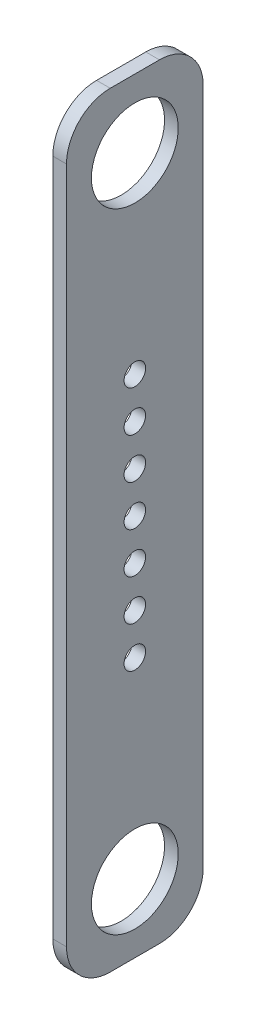
SolidWorks part; units mm, degrees
ref_plane "Front Plane" through (0, 0, 0) normal (1, 0, 0) x (0, 1, 0)
ref_plane "Top Plane" through (0, 0, 0) normal (0, 0, 1) x (0, 1, 0)
ref_plane "Right Plane" through (0, 0, 0) normal (0, 1, 0) x (-1, 0, 0)
sketch "Sketch1" plane through (0, 0, 0) normal (1, 0, 0) x (0, 1, 0)
  line L0 (38.1, 0) -> (-38.1, 0) construction
  line L1 (44.45, -7.9375) -> (-44.45, -7.9375)
  line L2 (44.45, -7.9375) -> (44.45, 7.9375)
  line L3 (44.45, 7.9375) -> (-44.45, 7.9375)
  line L4 (-44.45, -7.9375) -> (-44.45, 7.9375)
  line L5 (44.45, -7.9375) -> (-44.45, 7.9375) construction
  line L6 (44.45, 7.9375) -> (-44.45, -7.9375) construction
  point P0 (0, 0)
  point P9 (0, 0)
  dimension "D1" = 88.9
  dimension "D2" = 15.875
  dimension "D3" = 6.35
base flange "Base-Flange1" sketch "Sketch1" thickness 1.5875 reverse thickness direction no parameters "D1"=0.7366
sketch "Sketch6" plane through (0, 0, 0) normal (1, 0, 0) x (0, 1, 0)
  line L0 (44.45, 7.9375) -> (-44.45, 7.9375) construction
  line L1 (23.114, -7.9375) -> (-23.114, -7.9375) construction
  line L2 (23.114, -7.9375) -> (23.114, 7.9375)
  line L3 (23.114, 7.9375) -> (-23.114, 7.9375) construction
  line L4 (-23.114, -7.9375) -> (-23.114, 7.9375)
  line L5 (23.114, -7.9375) -> (-23.114, 7.9375) construction
  line L6 (23.114, 7.9375) -> (-23.114, -7.9375) construction
  point P0 (0, 0)
  dimension "D1" = 46.228
sketch "Sketch9" plane through (-1.5875, 0, 0) normal (-1, 0, 0) x (0, -1, 0)
  point P6 (0, 0)
  point P14 (-20.5228, 0)
  point P15 (-17.5777, 0)
hole_wizard "Ø2.5mm Dowel Hole1" positions "Sketch9" profile "Sketch10" hole size "Ø2.5" standard "ANSI Metric" end condition through all
sketch "Sketch10" plane through (-1.5875, 0, 0) normal (0, 1, 0) x (0, 0, 1)
  line L0 (0, 0) -> (0, 1.5875)
  line L1 (0, 1.5875) -> (1.25, 1.5875)
  line L2 (1.25, 1.5875) -> (1.25, 0)
  line L5 (1.25, 0) -> (0, 0)
  line L11 (0, -6.35) -> (0, 107.95) construction
  dimension "Thru Hole Dia." = 2.5
  dimension "Thru Hole Depth" = 1.5875
pattern_linear "LPattern1" count 4 spacing 4.75 along (0, -1, 0) count 4 spacing 4.75 along (0, 1, 0) of "Ø2.5mm Dowel Hole1"
fillet "Fillet1" radius 5.08 4 edges at (-0.7937, 44.45, 7.9375) (-0.7937, 44.45, -7.9375) (-0.7937, -44.45, 7.9375) (-0.7937, -44.45, -7.9375)
sketch "Sketch12" plane through (-1.5875, 0, 0) normal (-1, 0, 0) x (0, -1, 0)
  line L0 (-39.37, 7.9375) -> (39.37, 7.9375) construction
  line L2 (-44.45, -2.8575) -> (-44.45, 2.8575) construction
  line L3 (44.45, 2.8575) -> (44.45, -2.8575) construction
  point P0 (-36.5125, 0)
  point P8 (36.5125, 0)
  dimension "D1" = 7.9375
  dimension "D2" = 7.9375
  dimension "D3" = 7.9375
  dimension "D4" = 7.9375
hole_wizard "3/8 Clearance Hole1" positions "Sketch12" profile "Sketch13" hole size "3/8" standard "ANSI Inch" end condition through all
sketch "Sketch13" plane through (-1.5875, 36.5125, 0) normal (0, 1, 0) x (0, 0, 1)
  line L0 (0, 0) -> (0, 1.5875)
  line L1 (0, 1.5875) -> (5.0419, 1.5875)
  line L2 (5.0419, 1.5875) -> (5.0419, 0)
  line L5 (5.0419, 0) -> (0, 0)
  line L11 (0, -6.35) -> (0, 107.95) construction
  dimension "Thru Hole Dia." = 10.0838
  dimension "Thru Hole Depth" = 1.5875
sketch "Bend-Lines1" [suppressed] plane through (0, 0, 0) normal (0, 1, 0) x (1, 0, 0)
sketch "Bounding-Box1" [suppressed] plane through (0, 0, 0) normal (0, 1, 0) x (1, 0, 0)
sheet metal parameters "Sheet-Metal1" thickness 1.5875 parameters "D1"=0.7366
flat pattern "Flat-Pattern1" [suppressed]
sketch "Bend-Lines2" plane through (0, 0, 0) normal (1, 0, 0) x (0, 0, -1)
  line L0 (-6.35, -21.9918) -> (6.35, -21.9918) construction
  line L1 (6.35, 21.9918) -> (-6.35, 21.9918) construction
  line L2 (-6.35, -21.9918) -> (6.35, -21.9918) construction
  line L3 (6.35, 21.9918) -> (-6.35, 21.9918) construction
sketch3d "Bounding-Box2" [suppressed]
  line L0 (6.35, 41.275, 0) -> (6.35, -41.275, 0) construction
  line L1 (-6.35, 41.275, 0) -> (-6.35, -41.275, 0) construction
  line L2 (6.35, 41.275, 0) -> (-6.35, 41.275, 0) construction
  line L3 (6.35, -41.275, 0) -> (-6.35, -41.275, 0) construction
sheet metal parameters "Sheet-Metal3" thickness 1.5875 parameters "D1"=0.7366
flat pattern "Flat-Pattern1"
sketch "Bend-Lines2" plane through (0, 0, 0) normal (1, 0, 0) x (0, 0, -1)
  line L0 (-7.9375, -21.9918) -> (7.9375, -21.9918) construction
  line L1 (7.9375, 21.9918) -> (-7.9375, 21.9918) construction
  line L2 (-7.9375, -21.9918) -> (7.9375, -21.9918) construction
  line L3 (7.9375, 21.9918) -> (-7.9375, 21.9918) construction
sketch3d "Bounding-Box2" [suppressed]
  line L0 (7.9375, 44.45, 0) -> (7.9375, -44.45, 0) construction
  line L1 (-7.9375, 44.45, 0) -> (-7.9375, -44.45, 0) construction
  line L2 (7.9375, 44.45, 0) -> (-7.9375, 44.45, 0) construction
  line L3 (7.9375, -44.45, 0) -> (-7.9375, -44.45, 0) construction
bend of the flat pattern "Flatten-<SketchBend1>1"
bend of the flat pattern "Flatten-<SketchBend2>1"
sheet metal parameters "Sheet-Metal4" thickness 1.5875 parameters "D1"=0.7366
flat pattern "Flat-Pattern1"
sketch "Bend-Lines2" plane through (0, 0, 0) normal (1, 0, 0) x (0, 0, -1)
sketch3d "Bounding-Box2" [suppressed]
  line L0 (7.9375, -44.45, 0) -> (7.9375, 44.45, 0) construction
  line L1 (-7.9375, -44.45, 0) -> (-7.9375, 44.45, 0) construction
  line L2 (7.9375, -44.45, 0) -> (-7.9375, -44.45, 0) construction
  line L3 (7.9375, 44.45, 0) -> (-7.9375, 44.45, 0) construction
sheet metal parameters "Sheet-Metal5" thickness 1.5875 parameters "D1"=0.7366
flat pattern "Flat-Pattern1"
sketch "Bend-Lines2" plane through (0, 0, 0) normal (1, 0, 0) x (0, 0, -1)
sketch3d "Bounding-Box2" [suppressed]
  line L0 (7.9375, -44.45, 0) -> (7.9375, 44.45, 0) construction
  line L1 (-7.9375, -44.45, 0) -> (-7.9375, 44.45, 0) construction
  line L2 (7.9375, -44.45, 0) -> (-7.9375, -44.45, 0) construction
  line L3 (7.9375, 44.45, 0) -> (-7.9375, 44.45, 0) construction
